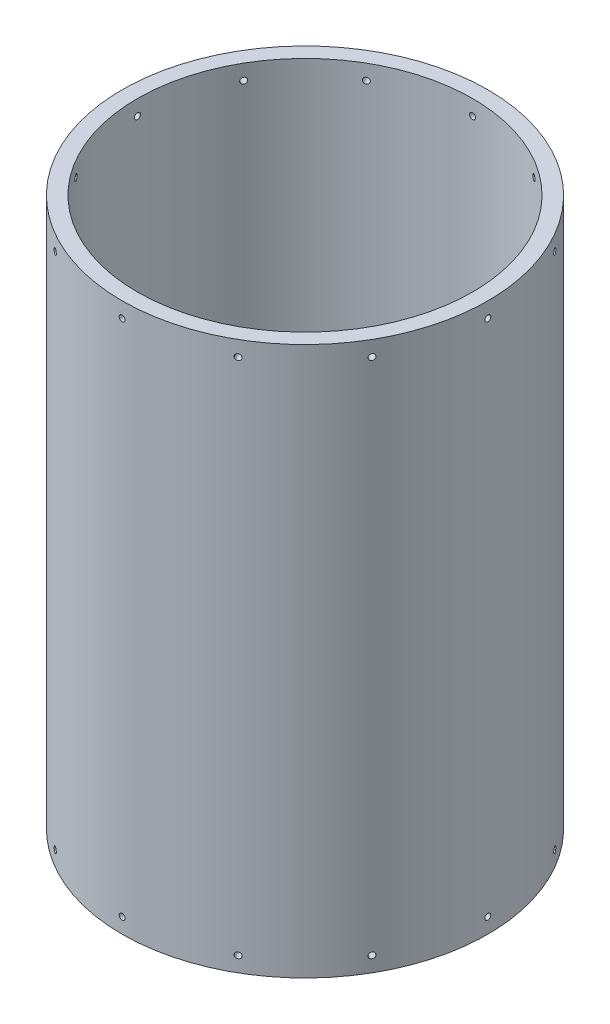
SolidWorks part; units mm, degrees
ref_plane "Front Plane" through (0, 0, 0) normal (0, 0, 1) x (1, 0, 0)
ref_plane "Top Plane" through (0, 0, 0) normal (0, 1, 0) x (1, 0, 0)
ref_plane "Right Plane" through (0, 0, 0) normal (1, 0, 0) x (0, 0, -1)
sketch "Sketch1" plane through (0, 0, 0) normal (0, 1, 0) x (1, 0, 0)
  circle A0 centre (0, 0) radius 152.4
  circle A1 centre (0, 0) radius 139.7
  dimension "D1" = 304.8
  dimension "D2" = 279.4
extrude "Boss-Extrude1" add sketch "Sketch1" along normal blind 457.2
ref_plane "Plane1" through (-152.4, 0, 0) normal (-1, 0, 0) x (0, 0, 1)
hole_wizard "#10 (0.1935) Diameter Hole1" positions "Sketch2" profile "Sketch3" hole size "#10" standard "ANSI Inch" end condition up to next
sketch "Sketch2" plane through (-152.4, 0, 0) normal (-1, 0, 0) x (0, 0, 1)
  line L0 (0, -167.64) -> (0, 167.64) construction
  line L1 (139.7, 457.2) -> (-139.7, 457.2) construction
  point P0 (0, 444.5)
  dimension "D1" = 12.7
sketch "Sketch3" plane through (-152.4, 444.5, 0) normal (0, 1, 0) x (0, 0, 1)
  line L0 (0, 0) -> (0, 343.2351)
  line L1 (0, 343.2351) -> (2.4574, 343.2351)
  line L2 (2.4574, 343.2351) -> (2.4574, 0)
  line L5 (2.4574, 0) -> (0, 0)
  line L11 (0, -6.35) -> (0, 107.95) construction
  dimension "Thru Hole Dia." = 4.9149
  dimension "Thru Hole Depth" = 343.2351
pattern_circular "CirPattern1" count 12 over 360 about axis through (0, 457.2, 0) along (0, -1, 0) of "#10 (0.1935) Diameter Hole1"
ref_plane "Plane2" through (0, 228.6, 0) normal (0, 1, 0) x (1, 0, 0)
mirror "Mirror1" about plane through (0, 228.6, 0) normal (0, 1, 0) of "CirPattern1"
